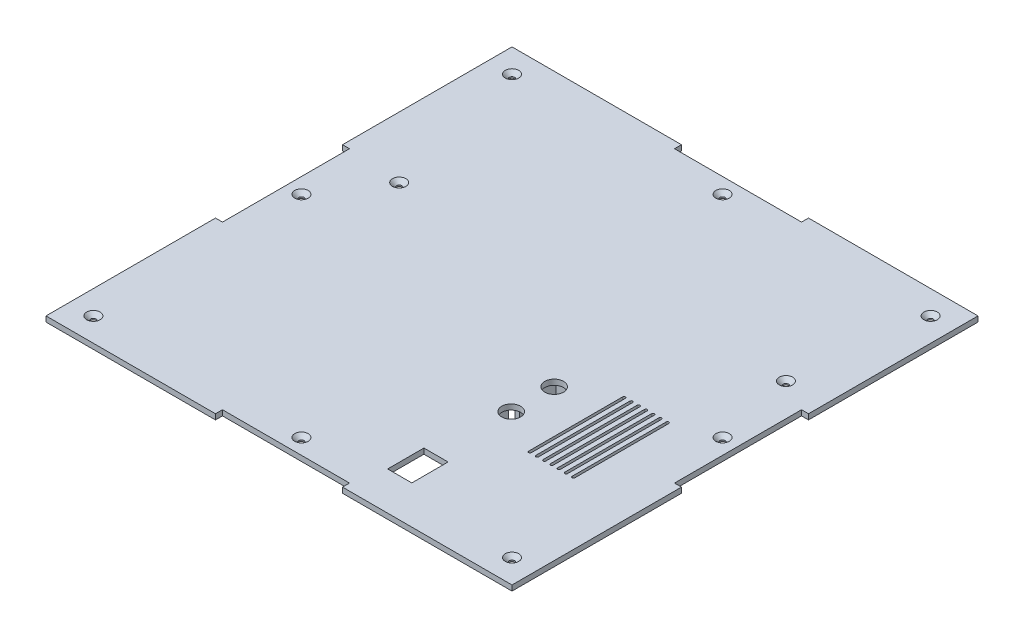
SolidWorks part; units mm, degrees
ref_plane "Front Plane" through (0, 0, 0) normal (0, 0, 1) x (1, 0, 0)
ref_plane "Top Plane" through (0, 0, 0) normal (0, 1, 0) x (1, 0, 0)
ref_plane "Right Plane" through (0, 0, 0) normal (1, 0, 0) x (0, 0, -1)
sketch "Sketch1" plane through (0, 0, 0) normal (0, 1, 0) x (1, 0, 0)
  line L0 (23.4, -87) -> (87, -87) construction
  line L1 (23.4, -84.4) -> (23.4, -87) construction
  line L2 (-23.4, -84.4) -> (23.4, -84.4) construction
  line L3 (-23.4, -87) -> (-23.4, -84.4) construction
  line L4 (-87, -87) -> (-23.4, -87) construction
  line L5 (-87, -23.4) -> (-87, -87) construction
  line L6 (-84.4, -23.4) -> (-87, -23.4) construction
  line L7 (-84.4, 23.4) -> (-84.4, -23.4) construction
  line L8 (-87, 23.4) -> (-84.4, 23.4) construction
  line L9 (-87, 87) -> (-87, 23.4) construction
  line L10 (-23.4, 87) -> (-87, 87) construction
  line L11 (-23.4, 84.4) -> (-23.4, 87) construction
  line L12 (23.4, 84.4) -> (-23.4, 84.4) construction
  line L13 (23.4, 87) -> (23.4, 84.4) construction
  line L14 (87, 87) -> (23.4, 87) construction
  line L15 (87, 23.4) -> (87, 87) construction
  line L16 (84.4, 23.4) -> (87, 23.4) construction
  line L17 (84.4, -23.4) -> (84.4, 23.4) construction
  line L18 (87, -23.4) -> (84.4, -23.4) construction
  line L19 (87, -87) -> (87, -23.4) construction
  line L20 (23.65, -86.75) -> (86.75, -86.75)
  line L21 (86.75, -86.75) -> (86.75, -23.65)
  line L22 (86.75, -23.65) -> (84.15, -23.65)
  line L23 (84.15, -23.65) -> (84.15, 23.65)
  line L24 (84.15, 23.65) -> (86.75, 23.65)
  line L25 (86.75, 23.65) -> (86.75, 86.75)
  line L26 (86.75, 86.75) -> (23.65, 86.75)
  line L27 (23.65, 86.75) -> (23.65, 84.15)
  line L28 (23.65, 84.15) -> (-23.65, 84.15)
  line L29 (-23.65, 84.15) -> (-23.65, 86.75)
  line L30 (-23.65, 86.75) -> (-86.75, 86.75)
  line L31 (-86.75, 86.75) -> (-86.75, 23.65)
  line L32 (-86.75, 23.65) -> (-84.15, 23.65)
  line L33 (-84.15, 23.65) -> (-84.15, -23.65)
  line L34 (-84.15, -23.65) -> (-86.75, -23.65)
  line L35 (-86.75, -23.65) -> (-86.75, -86.75)
  line L36 (-86.75, -86.75) -> (-23.65, -86.75)
  line L37 (-23.65, -86.75) -> (-23.65, -84.15)
  line L38 (-23.65, -84.15) -> (23.65, -84.15)
  line L39 (23.65, -84.15) -> (23.65, -86.75)
  point P20 (0, 84.4)
  point P22 (84.4, 0)
  dimension "D1" = 174
  dimension "D2" = 63.6
  dimension "D3" = 46.8
  dimension "D4" = 174
  dimension "D5" = 63.6
  dimension "D6" = 46.8
  dimension "D7" = 46.8
  dimension "D8" = 63.6
  dimension "D9" = 63.6
  dimension "D10" = 46.8
  dimension "D11" = 2.6
  dimension "D12" = 2.6
  dimension "D13" = 2.6
  dimension "D14" = 2.6
  dimension "D15" = 0.25
extrude "Boss-Extrude1" add sketch "Sketch1" along normal blind 2
sketch "Sketch2" plane through (0, 0, 0) normal (0, -1, 0) x (1, 0, 0)
  circle A0 centre (-77.9289, 77.9289) radius 1
  circle A1 centre (0, 78.4) radius 1
  circle A2 centre (77.9289, 77.9289) radius 1
  circle A3 centre (-78.4, 0) radius 1
  circle A4 centre (78.4, 0) radius 1
  circle A5 centre (72, -30) radius 1
  circle A6 centre (-64, -22) radius 1
  circle A7 centre (-77.9289, -77.9289) radius 1
  circle A8 centre (0, -78.4) radius 1
  circle A9 centre (77.9289, -77.9289) radius 1
  dimension "D1" = 2
  dimension "D2" = 2
  dimension "D3" = 2
  dimension "D4" = 2
  dimension "D5" = 2
  dimension "D6" = 2
  dimension "D7" = 2
  dimension "D8" = 2
  dimension "D9" = 2
  dimension "D10" = 2
extrude "Cut-Extrude1" cut sketch "Sketch2" against normal through all
chamfer "Chamfer1" distance 1.5 angle 45 10 edges at (-77.9289, 2, -78.9289) (0, 2, -79.4) (77.9289, 2, -78.9289) (72, 2, -31) (78.4, 2, -1) (-64, 2, -23) (-78.4, 2, -1) (-77.9289, 2, 76.9289) (0, 2, 77.4) (77.9289, 2, 76.9289)
sketch "Sketch4" plane through (0, 0, 0) normal (0, -1, 0) x (1, 0, 0)
  line L0 (47.2, 40.5) -> (47.2, 5.5) construction
  line L1 (44.2, 40.5) -> (66.2, 40.5) construction
  line L2 (44.2, 40.5) -> (44.2, 5.5) construction
  line L3 (44.2, 5.5) -> (66.2, 5.5) construction
  line L4 (66.2, 40.5) -> (66.2, 5.5) construction
  line L5 (47.7, 40.5) -> (47.7, 5.5)
  line L6 (46.7, 40.5) -> (46.7, 5.5)
  line L7 (44.2, 44) -> (52.2, 44) construction
  line L8 (58.2, 2) -> (66.2, 2) construction
  line L9 (66.2, 44) -> (66.2, 38) construction
  line L10 (44.2, 44) -> (44.2, 38) construction
  line L11 (49.9, 40.5) -> (49.9, 5.5) construction
  line L12 (50.4, 40.5) -> (50.4, 5.5)
  line L13 (49.4, 40.5) -> (49.4, 5.5)
  line L14 (52.6, 40.5) -> (52.6, 5.5) construction
  line L15 (53.1, 40.5) -> (53.1, 5.5)
  line L16 (52.1, 40.5) -> (52.1, 5.5)
  line L17 (55.3, 40.5) -> (55.3, 5.5) construction
  line L18 (55.8, 40.5) -> (55.8, 5.5)
  line L19 (54.8, 40.5) -> (54.8, 5.5)
  line L20 (58, 40.5) -> (58, 5.5) construction
  line L21 (58.5, 40.5) -> (58.5, 5.5)
  line L22 (57.5, 40.5) -> (57.5, 5.5)
  line L23 (60.7, 40.5) -> (60.7, 5.5) construction
  line L24 (61.2, 40.5) -> (61.2, 5.5)
  line L25 (60.2, 40.5) -> (60.2, 5.5)
  line L26 (63.4, 40.5) -> (63.4, 5.5) construction
  line L27 (63.9, 40.5) -> (63.9, 5.5)
  line L28 (62.9, 40.5) -> (62.9, 5.5)
  arc A0 (47.7, 40.5) -> (46.7, 40.5) centre (47.2, 40.5) ccw
  arc A1 (46.7, 5.5) -> (47.7, 5.5) centre (47.2, 5.5) ccw
  arc A2 (50.4, 40.5) -> (49.4, 40.5) centre (49.9, 40.5) ccw
  arc A3 (49.4, 5.5) -> (50.4, 5.5) centre (49.9, 5.5) ccw
  arc A4 (53.1, 40.5) -> (52.1, 40.5) centre (52.6, 40.5) ccw
  arc A5 (52.1, 5.5) -> (53.1, 5.5) centre (52.6, 5.5) ccw
  arc A6 (55.8, 40.5) -> (54.8, 40.5) centre (55.3, 40.5) ccw
  arc A7 (54.8, 5.5) -> (55.8, 5.5) centre (55.3, 5.5) ccw
  arc A8 (58.5, 40.5) -> (57.5, 40.5) centre (58, 40.5) ccw
  arc A9 (57.5, 5.5) -> (58.5, 5.5) centre (58, 5.5) ccw
  arc A10 (61.2, 40.5) -> (60.2, 40.5) centre (60.7, 40.5) ccw
  arc A11 (60.2, 5.5) -> (61.2, 5.5) centre (60.7, 5.5) ccw
  arc A12 (63.9, 40.5) -> (62.9, 40.5) centre (63.4, 40.5) ccw
  arc A13 (62.9, 5.5) -> (63.9, 5.5) centre (63.4, 5.5) ccw
  point P4 (47.2, 5.5)
  point P8 (47.2, 23)
  point P15 (0, 0)
  point P25 (49.9, 23)
  point P32 (52.6, 23)
  point P39 (55.3, 23)
  point P46 (58, 23)
  point P53 (60.7, 23)
  point P60 (63.4, 23)
  dimension "D2" = 3
  dimension "D1" = 1
  dimension "D3" = 3.5
  dimension "D4" = 3.5
  dimension "D6" = 4.6
  dimension "D5" = 7
extrude "Cut-Extrude3" cut sketch "Sketch4" against normal through all
sketch "Sketch3" plane through (0, 0, 0) normal (0, -1, 0) x (1, 0, 0)
  line L1 (26.2, 72.5) -> (35.2, 72.5)
  line L2 (26.2, 72.5) -> (26.2, 59)
  line L3 (26.2, 59) -> (35.2, 59)
  line L4 (35.2, 72.5) -> (35.2, 59)
  line L5 (86.75, 86.75) -> (86.75, 23.65) construction
  line L6 (41.95, 59) -> (68.45, 59) construction
  dimension "D1" = 13.5
  dimension "D2" = 9
  dimension "D4" = 51.55
extrude "Cut-Extrude2" cut sketch "Sketch3" against normal through all
sketch "Sketch5" plane through (0, 0, 0) normal (0, -1, 0) x (1, 0, 0)
  line L0 (35.2, 59) -> (35.2, 72.5) construction
  line L1 (23.7, 38.75) -> (37.7, 38.75)
  line L2 (23.7, 38.75) -> (23.7, 7.25)
  line L3 (23.7, 7.25) -> (37.7, 7.25)
  line L4 (37.7, 38.75) -> (37.7, 7.25)
  line L5 (47.7, 5.5) -> (47.7, 40.5) construction
  line L6 (42.7, 0.5) -> (42.7, 45.5) construction
  line L7 (22.2, 40.25) -> (22.2, 5.75)
  line L8 (22.2, 5.75) -> (39.2, 5.75)
  line L9 (39.2, 40.25) -> (39.2, 5.75)
  line L10 (22.2, 40.25) -> (39.2, 40.25)
  point P6 (35.2, 65.75)
  point P7 (40.4831, 28.4107)
  point P8 (37.4234, 9.1381)
  point P11 (47.7, 23)
  point P12 (37.7, 23)
  dimension "D1" = 14
  dimension "D2" = 31.5
  dimension "D3" = 5
  dimension "D4" = 1.5
extrude "Boss-Extrude2" add sketch "Sketch5" along normal blind 10 contours L10 L7 L8 L9 L1 L4 L3 L2 region at (30.7, 0, 39.8654)
sketch "Sketch7" plane through (0, 0, 0) normal (0, -1, 0) x (1, 0, 0)
  line L0 (23.7, 38.75) -> (37.7, 38.75) construction
  line L1 (30.7, 31) -> (30.7, 15) construction
  line L2 (37.7, 38.75) -> (37.7, 7.25) construction
  circle A0 centre (30.7, 15) radius 3.5
  circle A1 centre (30.7, 31) radius 3.5
  point P8 (30.7, 38.75)
  point P9 (37.7, 23)
  point P10 (30.7, 23)
  dimension "D1" = 7
  dimension "D2" = 7
  dimension "D3" = 16
extrude "Cut-Extrude5" cut sketch "Sketch7" against normal through all
sketch "Sketch6" plane through (0, -10, 0) normal (0, -1, 0) x (1, 0, 0)
  line L1 (22.2, 25) -> (23.7, 25)
  line L2 (22.2, 25) -> (22.2, 21)
  line L3 (22.2, 21) -> (23.7, 21)
  line L4 (23.7, 25) -> (23.7, 21)
  line L5 (23.7, 38.75) -> (23.7, 7.25) construction
  line L8 (22.2, 40.25) -> (22.2, 5.75) construction
  point P4 (22.2, 25.6443)
  point P9 (22.2, 23)
  point P10 (23.7, 23)
  dimension "D1" = 4
extrude "Cut-Extrude4" cut sketch "Sketch6" against normal up to surface (10 mm away) up to face at (30.7, 0, 23)
sketch "Sketch8" plane through (0, 0, 0) normal (0, -1, 0) x (1, 0, 0)
  circle A0 centre (30.7, 31) radius 5
  circle A1 centre (30.7, 15) radius 5
  circle A2 centre (30.7, 31) radius 6
  circle A3 centre (30.7, 15) radius 6
  dimension "D1" = 10
  dimension "D2" = 10
  dimension "D3" = 1
  dimension "D4" = 1
extrude "Boss-Extrude3" add sketch "Sketch8" along normal blind 1
